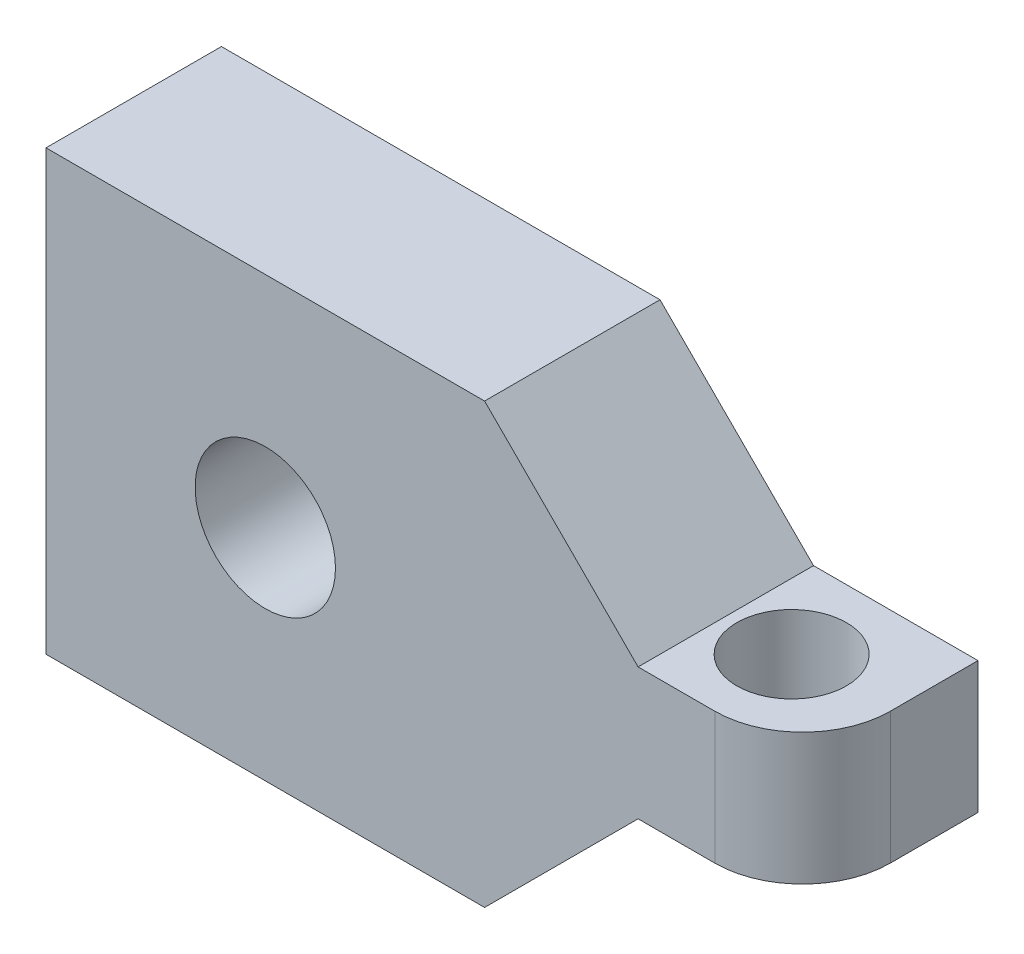
SolidWorks part; units mm, degrees
ref_plane "Front Plane" through (0, 0, 0) normal (1, 0, 0) x (0, 1, 0)
ref_plane "Top Plane" through (0, 0, 0) normal (0, 0, 1) x (0, 1, 0)
ref_plane "Right Plane" through (0, 0, 0) normal (0, 1, 0) x (-1, 0, 0)
sketch "Sketch1" plane through (0, 0, 0) normal (0, 0, 1) x (0, 1, 0)
  line L1 (-5, 10) -> (5, 10)
  line L2 (-5, 10) -> (-5, -10)
  line L3 (-5, -10) -> (5, -10)
  line L4 (5, 10) -> (5, -10)
  line L5 (-5, 10) -> (5, -10) construction
  line L6 (-5, -10) -> (5, 10) construction
  point P0 (0, 0)
  dimension "D1" = 10
  dimension "D2" = 20
extrude "Boss-Extrude1" add sketch "Sketch1" along normal blind 4
sketch "Sketch2" plane through (0, 0, 4) normal (0, 0, 1) x (1, 0, 0)
  line L0 (-10, 5) -> (-10, -5) construction
  circle A0 centre (-5, 0) radius 1.6
  dimension "D1" = 3.2
  dimension "D2" = 5
extrude "Cut-Extrude1" cut sketch "Sketch2" against normal through all
sketch "Sketch3" plane through (0, -5, 0) normal (0, -1, 0) x (1, 0, 0)
  line L0 (10, 4) -> (10, 0) construction
  circle A0 centre (5, 2) radius 1.25
  point P2 (10, 2)
  dimension "D1" = 2.5
  dimension "D2" = 5
extrude "Cut-Extrude2" cut sketch "Sketch3" against normal through all
sketch "Sketch4" plane through (0, 0, 4) normal (0, 0, 1) x (1, 0, 0)
  line L0 (-10, -5) -> (10, -5) construction
  line L1 (10, -5) -> (7.25, -5)
  line L2 (10, -5) -> (10, 5)
  line L3 (10, 5) -> (7.25, 5)
  line L4 (7.25, -5) -> (7.25, 5)
  line L5 (10, 5) -> (-10, 5) construction
  line L6 (6.25, -5) -> (6.25, 5) construction
  dimension "D1" = 1
extrude "Cut-Extrude3" cut sketch "Sketch4" against normal through all
sketch "Sketch5" plane through (0, 0, 4) normal (0, 0, 1) x (1, 0, 0)
  line L0 (7.25, 5) -> (-10, 5) construction
  line L1 (0, 5) -> (7.25, 5)
  line L2 (0, 5) -> (0, 1.5)
  line L3 (0, 1.5) -> (7.25, 1.5)
  line L4 (7.25, 5) -> (7.25, 1.5)
  line L5 (7.25, 5) -> (7.25, -5) construction
  line L6 (-10, -5) -> (7.25, -5) construction
  line L7 (0, -5) -> (7.25, -5)
  line L8 (0, -5) -> (0, -1.5)
  line L9 (0, -1.5) -> (7.25, -1.5)
  line L10 (7.25, -5) -> (7.25, -1.5)
  circle A0 centre (-5, 0) radius 1.6 construction
  dimension "D1" = 3
  dimension "D2" = 5
extrude "Cut-Extrude4" cut sketch "Sketch5" against normal through all
chamfer "Chamfer1" distance 3.5 angle 45 2 edges at (0, 1.5, 2) (0, -1.5, 2)
fillet "Fillet1" radius 2 1 edges at (7.25, 0, 4)
